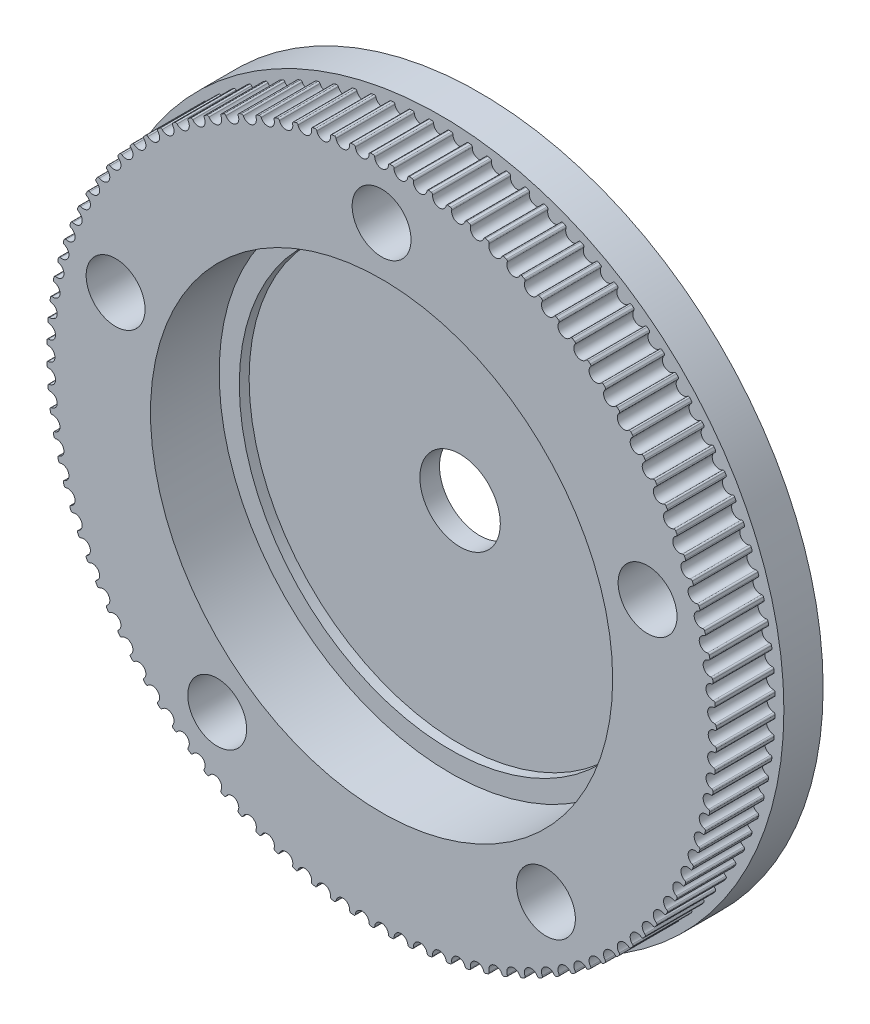
SolidWorks part; units mm, degrees
ref_plane "前视基准面" through (0, 0, 0) normal (0, 0, 1) x (1, 0, 0)
ref_plane "上视基准面" through (0, 0, 0) normal (0, 1, 0) x (1, 0, 0)
ref_plane "右视基准面" through (0, 0, 0) normal (1, 0, 0) x (0, 0, -1)
sketch "草图1" plane through (0, 0, 0) normal (0, 0, 1) x (1, 0, 0)
  circle A0 centre (0, 0) radius 35
  circle A1 centre (0, 0) radius 4.1
  dimension "D1" = 70
  dimension "D2" = 8.2
extrude "凸台-拉伸1" add sketch "草图1" along normal blind 4
sketch "草图2" plane through (0, 0, 4) normal (0, 0, 1) x (1, 0, 0)
  circle A0 centre (0, 0) radius 4.1 construction
  circle A1 centre (0, 0) radius 4.1
  arc B0 (1.1216, 34.1041) -> (0.8633, 34.1116) centre (0, 0) ccw
  arc B1 (1.2763, 33.9415) -> (1.1216, 34.1041) centre (1.1163, 33.9441) ccw
  arc B2 (0.8633, 34.1116) -> (0.6994, 33.9583) centre (0.8593, 33.9516) ccw
  arc B3 (1.2763, 33.9415) -> (2.6727, 33.8602) centre (1.9762, 33.93) ccw
  arc B4 (-0.8633, 34.1116) -> (-1.1216, 34.1041) centre (0, 0) ccw
  arc B5 (-0.6994, 33.9583) -> (-0.8633, 34.1116) centre (-0.8593, 33.9516) ccw
  arc B6 (-1.1216, 34.1041) -> (-1.2763, 33.9415) centre (-1.1163, 33.9441) ccw
  arc B7 (-0.6994, 33.9583) -> (0.6994, 33.9583) centre (0, 33.9875) ccw
  arc B8 (-2.8453, 34.0037) -> (-3.1027, 33.9812) centre (0, 0) ccw
  arc B9 (-2.6727, 33.8602) -> (-2.8453, 34.0037) centre (-2.8319, 33.8442) ccw
  arc B10 (-3.1027, 33.9812) -> (-3.2477, 33.8099) centre (-3.0881, 33.8218) ccw
  arc B11 (-2.6727, 33.8602) -> (-1.2763, 33.9415) centre (-1.9762, 33.93) ccw
  arc B12 (-4.8176, 33.7807) -> (-5.0732, 33.7433) centre (0, 0) ccw
  arc B13 (-4.637, 33.6475) -> (-4.8176, 33.7807) centre (-4.795, 33.6223) ccw
  arc B14 (-5.0732, 33.7433) -> (-5.208, 33.5638) centre (-5.0494, 33.585) ccw
  arc B15 (-4.637, 33.6475) -> (-3.2477, 33.8099) centre (-3.9457, 33.7577) ccw
  arc B16 (-6.7736, 33.4434) -> (-7.0266, 33.3912) centre (0, 0) ccw
  arc B17 (-6.5856, 33.321) -> (-6.7736, 33.4434) centre (-6.7418, 33.2866) ccw
  arc B18 (-7.0266, 33.3912) -> (-7.1508, 33.2042) centre (-6.9937, 33.2346) ccw
  arc B19 (-6.5856, 33.321) -> (-5.208, 33.5638) centre (-5.9019, 33.4712) ccw
  arc B20 (-8.7067, 32.993) -> (-8.9563, 32.9261) centre (0, 0) ccw
  arc B21 (-8.5119, 32.8817) -> (-8.7067, 32.993) centre (-8.6659, 32.8383) ccw
  arc B22 (-8.9563, 32.9261) -> (-9.0693, 32.7323) centre (-8.9143, 32.7717) ccw
  arc B23 (-8.5119, 32.8817) -> (-7.1508, 33.2042) centre (-7.8381, 33.0714) ccw
  arc B24 (-10.6103, 32.4309) -> (-10.8556, 32.3497) centre (0, 0) ccw
  arc B25 (-10.4094, 32.3311) -> (-10.6103, 32.4309) centre (-10.5606, 32.2789) ccw
  arc B26 (-10.8556, 32.3497) -> (-10.9572, 32.1496) centre (-10.8047, 32.198) ccw
  arc B27 (-10.4094, 32.3311) -> (-9.0693, 32.7323) centre (-9.7477, 32.5597) ccw
  arc B28 (-12.4781, 31.7591) -> (-12.7182, 31.6637) centre (0, 0) ccw
  arc B29 (-12.2716, 31.6712) -> (-12.4781, 31.7591) centre (-12.4196, 31.6102) ccw
  arc B30 (-12.7182, 31.6637) -> (-12.808, 31.4581) centre (-12.6586, 31.5153) ccw
  arc B31 (-12.2716, 31.6712) -> (-10.9572, 32.1496) centre (-11.6244, 31.9378) ccw
  arc B32 (-14.3036, 30.9799) -> (-14.5378, 30.8707) centre (0, 0) ccw
  arc B33 (-14.0924, 30.904) -> (-14.3036, 30.9799) centre (-14.2365, 30.8346) ccw
  arc B34 (-14.5378, 30.8707) -> (-14.6155, 30.6601) centre (-14.4696, 30.7259) ccw
  arc B35 (-14.0924, 30.904) -> (-12.808, 31.4581) centre (-13.4618, 31.2079) ccw
  arc B36 (-16.0807, 30.0958) -> (-16.3081, 29.9731) centre (0, 0) ccw
  arc B37 (-15.8655, 30.0324) -> (-16.0807, 30.0958) centre (-16.0053, 29.9547) ccw
  arc B38 (-16.3081, 29.9731) -> (-16.3735, 29.7584) centre (-16.2317, 29.8326) ccw
  arc B39 (-15.8655, 30.0324) -> (-14.6155, 30.6601) centre (-15.2536, 30.3723) ccw
  arc B40 (-17.8034, 29.1098) -> (-18.0233, 28.9742) centre (0, 0) ccw
  arc B41 (-17.5848, 29.0591) -> (-17.8034, 29.1098) centre (-17.7199, 28.9733) ccw
  arc B42 (-18.0233, 28.9742) -> (-18.0761, 28.7561) centre (-17.9388, 28.8383) ccw
  arc B43 (-17.5848, 29.0591) -> (-16.3735, 29.7584) centre (-16.9937, 29.434) ccw
  arc B44 (-19.4659, 28.0254) -> (-19.6775, 27.8772) centre (0, 0) ccw
  arc B45 (-19.2447, 27.9874) -> (-19.4659, 28.0254) centre (-19.3746, 27.894) ccw
  arc B46 (-19.6775, 27.8772) -> (-19.7175, 27.6564) centre (-19.5853, 27.7465) ccw
  arc B47 (-19.2447, 27.9874) -> (-18.0761, 28.7561) centre (-18.6764, 28.3961) ccw
  arc B48 (-21.0625, 26.8462) -> (-21.2652, 26.6859) centre (0, 0) ccw
  arc B49 (-20.8395, 26.8211) -> (-21.0625, 26.8462) centre (-20.9637, 26.7203) ccw
  arc B50 (-21.2652, 26.6859) -> (-21.2922, 26.4631) centre (-21.1655, 26.5608) ccw
  arc B51 (-20.8395, 26.8211) -> (-19.7175, 27.6564) centre (-20.2959, 27.2622) ccw
  arc B52 (-22.5878, 25.5761) -> (-22.7808, 25.4043) centre (0, 0) ccw
  arc B53 (-22.3637, 25.564) -> (-22.5878, 25.5761) centre (-22.4819, 25.4561) ccw
  arc B54 (-22.7808, 25.4043) -> (-22.7949, 25.1803) centre (-22.674, 25.2852) ccw
  arc B55 (-22.3637, 25.564) -> (-21.2922, 26.4631) centre (-21.8467, 26.0359) ccw
  arc B56 (-24.0367, 24.2194) -> (-24.2194, 24.0367) centre (0, 0) ccw
  arc B57 (-23.8123, 24.2204) -> (-24.0367, 24.2194) centre (-23.924, 24.1059) ccw
  arc B58 (-24.2194, 24.0367) -> (-24.2204, 23.8123) centre (-24.1059, 23.924) ccw
  arc B59 (-23.8123, 24.2204) -> (-22.7949, 25.1803) centre (-23.3236, 24.7216) ccw
  arc B60 (-25.4043, 22.7808) -> (-25.5761, 22.5878) centre (0, 0) ccw
  arc B61 (-25.1803, 22.7949) -> (-25.4043, 22.7808) centre (-25.2852, 22.674) ccw
  arc B62 (-25.5761, 22.5878) -> (-25.564, 22.3637) centre (-25.4561, 22.4819) ccw
  arc B63 (-25.1803, 22.7949) -> (-24.2204, 23.8123) centre (-24.7216, 23.3236) ccw
  arc B64 (-26.6859, 21.2652) -> (-26.8462, 21.0625) centre (0, 0) ccw
  arc B65 (-26.4631, 21.2922) -> (-26.6859, 21.2652) centre (-26.5608, 21.1655) ccw
  arc B66 (-26.8462, 21.0625) -> (-26.8211, 20.8395) centre (-26.7203, 20.9637) ccw
  arc B67 (-26.4631, 21.2922) -> (-25.564, 22.3637) centre (-26.0359, 21.8467) ccw
  arc B68 (-27.8772, 19.6775) -> (-28.0254, 19.4659) centre (0, 0) ccw
  arc B69 (-27.6564, 19.7175) -> (-27.8772, 19.6775) centre (-27.7465, 19.5853) ccw
  arc B70 (-28.0254, 19.4659) -> (-27.9874, 19.2447) centre (-27.894, 19.3746) ccw
  arc B71 (-27.6564, 19.7175) -> (-26.8211, 20.8395) centre (-27.2622, 20.2959) ccw
  arc B72 (-28.9742, 18.0233) -> (-29.1098, 17.8034) centre (0, 0) ccw
  arc B73 (-28.7561, 18.0761) -> (-28.9742, 18.0233) centre (-28.8383, 17.9388) ccw
  arc B74 (-29.1098, 17.8034) -> (-29.0591, 17.5848) centre (-28.9733, 17.7199) ccw
  arc B75 (-28.7561, 18.0761) -> (-27.9874, 19.2447) centre (-28.3961, 18.6764) ccw
  arc B76 (-29.9731, 16.3081) -> (-30.0958, 16.0807) centre (0, 0) ccw
  arc B77 (-29.7584, 16.3735) -> (-29.9731, 16.3081) centre (-29.8326, 16.2317) ccw
  arc B78 (-30.0958, 16.0807) -> (-30.0324, 15.8655) centre (-29.9547, 16.0053) ccw
  arc B79 (-29.7584, 16.3735) -> (-29.0591, 17.5848) centre (-29.434, 16.9937) ccw
  arc B80 (-30.8707, 14.5378) -> (-30.9799, 14.3036) centre (0, 0) ccw
  arc B81 (-30.6601, 14.6155) -> (-30.8707, 14.5378) centre (-30.7259, 14.4696) ccw
  arc B82 (-30.9799, 14.3036) -> (-30.904, 14.0924) centre (-30.8346, 14.2365) ccw
  arc B83 (-30.6601, 14.6155) -> (-30.0324, 15.8655) centre (-30.3723, 15.2536) ccw
  arc B84 (-31.6637, 12.7182) -> (-31.7591, 12.4781) centre (0, 0) ccw
  arc B85 (-31.4581, 12.808) -> (-31.6637, 12.7182) centre (-31.5153, 12.6586) ccw
  arc B86 (-31.7591, 12.4781) -> (-31.6712, 12.2716) centre (-31.6102, 12.4196) ccw
  arc B87 (-31.4581, 12.808) -> (-30.904, 14.0924) centre (-31.2079, 13.4618) ccw
  arc B88 (-32.3497, 10.8556) -> (-32.4309, 10.6103) centre (0, 0) ccw
  arc B89 (-32.1496, 10.9572) -> (-32.3497, 10.8556) centre (-32.198, 10.8047) ccw
  arc B90 (-32.4309, 10.6103) -> (-32.3311, 10.4094) centre (-32.2789, 10.5606) ccw
  arc B91 (-32.1496, 10.9572) -> (-31.6712, 12.2716) centre (-31.9378, 11.6244) ccw
  arc B92 (-32.9261, 8.9563) -> (-32.993, 8.7067) centre (0, 0) ccw
  arc B93 (-32.7323, 9.0693) -> (-32.9261, 8.9563) centre (-32.7717, 8.9143) ccw
  arc B94 (-32.993, 8.7067) -> (-32.8817, 8.5119) centre (-32.8383, 8.6659) ccw
  arc B95 (-32.7323, 9.0693) -> (-32.3311, 10.4094) centre (-32.5597, 9.7477) ccw
  arc B96 (-33.3912, 7.0266) -> (-33.4434, 6.7736) centre (0, 0) ccw
  arc B97 (-33.2042, 7.1508) -> (-33.3912, 7.0266) centre (-33.2346, 6.9937) ccw
  arc B98 (-33.4434, 6.7736) -> (-33.321, 6.5856) centre (-33.2866, 6.7418) ccw
  arc B99 (-33.2042, 7.1508) -> (-32.8817, 8.5119) centre (-33.0714, 7.8381) ccw
  arc B100 (-33.7433, 5.0732) -> (-33.7807, 4.8176) centre (0, 0) ccw
  arc B101 (-33.5638, 5.208) -> (-33.7433, 5.0732) centre (-33.585, 5.0494) ccw
  arc B102 (-33.7807, 4.8176) -> (-33.6475, 4.637) centre (-33.6223, 4.795) ccw
  arc B103 (-33.5638, 5.208) -> (-33.321, 6.5856) centre (-33.4712, 5.9019) ccw
  arc B104 (-33.9812, 3.1027) -> (-34.0037, 2.8453) centre (0, 0) ccw
  arc B105 (-33.8099, 3.2477) -> (-33.9812, 3.1027) centre (-33.8218, 3.0881) ccw
  arc B106 (-34.0037, 2.8453) -> (-33.8602, 2.6727) centre (-33.8442, 2.8319) ccw
  arc B107 (-33.8099, 3.2477) -> (-33.6475, 4.637) centre (-33.7577, 3.9457) ccw
  arc B108 (-34.1041, 1.1216) -> (-34.1116, 0.8633) centre (0, 0) ccw
  arc B109 (-33.9415, 1.2763) -> (-34.1041, 1.1216) centre (-33.9441, 1.1163) ccw
  arc B110 (-34.1116, 0.8633) -> (-33.9583, 0.6994) centre (-33.9516, 0.8593) ccw
  arc B111 (-33.9415, 1.2763) -> (-33.8602, 2.6727) centre (-33.93, 1.9762) ccw
  arc B112 (-34.1116, -0.8633) -> (-34.1041, -1.1216) centre (0, 0) ccw
  arc B113 (-33.9583, -0.6994) -> (-34.1116, -0.8633) centre (-33.9516, -0.8593) ccw
  arc B114 (-34.1041, -1.1216) -> (-33.9415, -1.2763) centre (-33.9441, -1.1163) ccw
  arc B115 (-33.9583, -0.6994) -> (-33.9583, 0.6994) centre (-33.9875, 0) ccw
  arc B116 (-34.0037, -2.8453) -> (-33.9812, -3.1027) centre (0, 0) ccw
  arc B117 (-33.8602, -2.6727) -> (-34.0037, -2.8453) centre (-33.8442, -2.8319) ccw
  arc B118 (-33.9812, -3.1027) -> (-33.8099, -3.2477) centre (-33.8218, -3.0881) ccw
  arc B119 (-33.8602, -2.6727) -> (-33.9415, -1.2763) centre (-33.93, -1.9762) ccw
  arc B120 (-33.7807, -4.8176) -> (-33.7433, -5.0732) centre (0, 0) ccw
  arc B121 (-33.6475, -4.637) -> (-33.7807, -4.8176) centre (-33.6223, -4.795) ccw
  arc B122 (-33.7433, -5.0732) -> (-33.5638, -5.208) centre (-33.585, -5.0494) ccw
  arc B123 (-33.6475, -4.637) -> (-33.8099, -3.2477) centre (-33.7577, -3.9457) ccw
  arc B124 (-33.4434, -6.7736) -> (-33.3912, -7.0266) centre (0, 0) ccw
  arc B125 (-33.321, -6.5856) -> (-33.4434, -6.7736) centre (-33.2866, -6.7418) ccw
  arc B126 (-33.3912, -7.0266) -> (-33.2042, -7.1508) centre (-33.2346, -6.9937) ccw
  arc B127 (-33.321, -6.5856) -> (-33.5638, -5.208) centre (-33.4712, -5.9019) ccw
  arc B128 (-32.993, -8.7067) -> (-32.9261, -8.9563) centre (0, 0) ccw
  arc B129 (-32.8817, -8.5119) -> (-32.993, -8.7067) centre (-32.8383, -8.6659) ccw
  arc B130 (-32.9261, -8.9563) -> (-32.7323, -9.0693) centre (-32.7717, -8.9143) ccw
  arc B131 (-32.8817, -8.5119) -> (-33.2042, -7.1508) centre (-33.0714, -7.8381) ccw
  arc B132 (-32.4309, -10.6103) -> (-32.3497, -10.8556) centre (0, 0) ccw
  arc B133 (-32.3311, -10.4094) -> (-32.4309, -10.6103) centre (-32.2789, -10.5606) ccw
  arc B134 (-32.3497, -10.8556) -> (-32.1496, -10.9572) centre (-32.198, -10.8047) ccw
  arc B135 (-32.3311, -10.4094) -> (-32.7323, -9.0693) centre (-32.5597, -9.7477) ccw
  arc B136 (-31.7591, -12.4781) -> (-31.6637, -12.7182) centre (0, 0) ccw
  arc B137 (-31.6712, -12.2716) -> (-31.7591, -12.4781) centre (-31.6102, -12.4196) ccw
  arc B138 (-31.6637, -12.7182) -> (-31.4581, -12.808) centre (-31.5153, -12.6586) ccw
  arc B139 (-31.6712, -12.2716) -> (-32.1496, -10.9572) centre (-31.9378, -11.6244) ccw
  arc B140 (-30.9799, -14.3036) -> (-30.8707, -14.5378) centre (0, 0) ccw
  arc B141 (-30.904, -14.0924) -> (-30.9799, -14.3036) centre (-30.8346, -14.2365) ccw
  arc B142 (-30.8707, -14.5378) -> (-30.6601, -14.6155) centre (-30.7259, -14.4696) ccw
  arc B143 (-30.904, -14.0924) -> (-31.4581, -12.808) centre (-31.2079, -13.4618) ccw
  arc B144 (-30.0958, -16.0807) -> (-29.9731, -16.3081) centre (0, 0) ccw
  arc B145 (-30.0324, -15.8655) -> (-30.0958, -16.0807) centre (-29.9547, -16.0053) ccw
  arc B146 (-29.9731, -16.3081) -> (-29.7584, -16.3735) centre (-29.8326, -16.2317) ccw
  arc B147 (-30.0324, -15.8655) -> (-30.6601, -14.6155) centre (-30.3723, -15.2536) ccw
  arc B148 (-29.1098, -17.8034) -> (-28.9742, -18.0233) centre (0, 0) ccw
  arc B149 (-29.0591, -17.5848) -> (-29.1098, -17.8034) centre (-28.9733, -17.7199) ccw
  arc B150 (-28.9742, -18.0233) -> (-28.7561, -18.0761) centre (-28.8383, -17.9388) ccw
  arc B151 (-29.0591, -17.5848) -> (-29.7584, -16.3735) centre (-29.434, -16.9938) ccw
  arc B152 (-28.0254, -19.4659) -> (-27.8772, -19.6775) centre (0, 0) ccw
  arc B153 (-27.9874, -19.2447) -> (-28.0254, -19.4659) centre (-27.894, -19.3746) ccw
  arc B154 (-27.8772, -19.6775) -> (-27.6564, -19.7175) centre (-27.7465, -19.5853) ccw
  arc B155 (-27.9874, -19.2447) -> (-28.7561, -18.0761) centre (-28.3961, -18.6764) ccw
  arc B156 (-26.8462, -21.0625) -> (-26.6859, -21.2652) centre (0, 0) ccw
  arc B157 (-26.8211, -20.8395) -> (-26.8462, -21.0625) centre (-26.7203, -20.9637) ccw
  arc B158 (-26.6859, -21.2652) -> (-26.4631, -21.2922) centre (-26.5608, -21.1655) ccw
  arc B159 (-26.8211, -20.8395) -> (-27.6564, -19.7175) centre (-27.2622, -20.2959) ccw
  arc B160 (-25.5761, -22.5878) -> (-25.4043, -22.7808) centre (0, 0) ccw
  arc B161 (-25.564, -22.3637) -> (-25.5761, -22.5878) centre (-25.4561, -22.4819) ccw
  arc B162 (-25.4043, -22.7808) -> (-25.1803, -22.7949) centre (-25.2852, -22.674) ccw
  arc B163 (-25.564, -22.3637) -> (-26.4631, -21.2922) centre (-26.0359, -21.8467) ccw
  arc B164 (-24.2194, -24.0367) -> (-24.0367, -24.2194) centre (0, 0) ccw
  arc B165 (-24.2204, -23.8123) -> (-24.2194, -24.0367) centre (-24.1059, -23.924) ccw
  arc B166 (-24.0367, -24.2194) -> (-23.8123, -24.2204) centre (-23.924, -24.1059) ccw
  arc B167 (-24.2204, -23.8123) -> (-25.1803, -22.7949) centre (-24.7216, -23.3236) ccw
  arc B168 (-22.7808, -25.4043) -> (-22.5878, -25.5761) centre (0, 0) ccw
  arc B169 (-22.7949, -25.1803) -> (-22.7808, -25.4043) centre (-22.674, -25.2852) ccw
  arc B170 (-22.5878, -25.5761) -> (-22.3637, -25.564) centre (-22.4819, -25.4561) ccw
  arc B171 (-22.7949, -25.1803) -> (-23.8123, -24.2204) centre (-23.3236, -24.7216) ccw
  arc B172 (-21.2652, -26.6859) -> (-21.0625, -26.8462) centre (0, 0) ccw
  arc B173 (-21.2922, -26.4631) -> (-21.2652, -26.6859) centre (-21.1655, -26.5608) ccw
  arc B174 (-21.0625, -26.8462) -> (-20.8395, -26.8211) centre (-20.9637, -26.7203) ccw
  arc B175 (-21.2922, -26.4631) -> (-22.3637, -25.564) centre (-21.8467, -26.0359) ccw
  arc B176 (-19.6775, -27.8772) -> (-19.4659, -28.0254) centre (0, 0) ccw
  arc B177 (-19.7175, -27.6564) -> (-19.6775, -27.8772) centre (-19.5853, -27.7465) ccw
  arc B178 (-19.4659, -28.0254) -> (-19.2447, -27.9874) centre (-19.3746, -27.894) ccw
  arc B179 (-19.7175, -27.6564) -> (-20.8395, -26.8211) centre (-20.2959, -27.2622) ccw
  arc B180 (-18.0233, -28.9742) -> (-17.8034, -29.1098) centre (0, 0) ccw
  arc B181 (-18.0761, -28.7561) -> (-18.0233, -28.9742) centre (-17.9388, -28.8383) ccw
  arc B182 (-17.8034, -29.1098) -> (-17.5848, -29.0591) centre (-17.7199, -28.9733) ccw
  arc B183 (-18.0761, -28.7561) -> (-19.2447, -27.9874) centre (-18.6764, -28.3961) ccw
  arc B184 (-16.3081, -29.9731) -> (-16.0807, -30.0958) centre (0, 0) ccw
  arc B185 (-16.3735, -29.7584) -> (-16.3081, -29.9731) centre (-16.2317, -29.8326) ccw
  arc B186 (-16.0807, -30.0958) -> (-15.8655, -30.0324) centre (-16.0053, -29.9547) ccw
  arc B187 (-16.3735, -29.7584) -> (-17.5848, -29.0591) centre (-16.9937, -29.434) ccw
  arc B188 (-14.5378, -30.8707) -> (-14.3036, -30.9799) centre (0, 0) ccw
  arc B189 (-14.6155, -30.6601) -> (-14.5378, -30.8707) centre (-14.4696, -30.7259) ccw
  arc B190 (-14.3036, -30.9799) -> (-14.0924, -30.904) centre (-14.2365, -30.8346) ccw
  arc B191 (-14.6155, -30.6601) -> (-15.8655, -30.0324) centre (-15.2536, -30.3723) ccw
  arc B192 (-12.7182, -31.6637) -> (-12.4781, -31.7591) centre (0, 0) ccw
  arc B193 (-12.808, -31.4581) -> (-12.7182, -31.6637) centre (-12.6586, -31.5153) ccw
  arc B194 (-12.4781, -31.7591) -> (-12.2716, -31.6712) centre (-12.4196, -31.6102) ccw
  arc B195 (-12.808, -31.4581) -> (-14.0924, -30.904) centre (-13.4618, -31.2079) ccw
  arc B196 (-10.8556, -32.3497) -> (-10.6103, -32.4309) centre (0, 0) ccw
  arc B197 (-10.9572, -32.1496) -> (-10.8556, -32.3497) centre (-10.8047, -32.198) ccw
  arc B198 (-10.6103, -32.4309) -> (-10.4094, -32.3311) centre (-10.5606, -32.2789) ccw
  arc B199 (-10.9572, -32.1496) -> (-12.2716, -31.6712) centre (-11.6244, -31.9378) ccw
  arc B200 (-8.9563, -32.9261) -> (-8.7067, -32.993) centre (0, 0) ccw
  arc B201 (-9.0693, -32.7323) -> (-8.9563, -32.9261) centre (-8.9143, -32.7717) ccw
  arc B202 (-8.7067, -32.993) -> (-8.5119, -32.8817) centre (-8.6659, -32.8383) ccw
  arc B203 (-9.0693, -32.7323) -> (-10.4094, -32.3311) centre (-9.7477, -32.5597) ccw
  arc B204 (-7.0266, -33.3912) -> (-6.7736, -33.4434) centre (0, 0) ccw
  arc B205 (-7.1508, -33.2042) -> (-7.0266, -33.3912) centre (-6.9937, -33.2346) ccw
  arc B206 (-6.7736, -33.4434) -> (-6.5856, -33.321) centre (-6.7418, -33.2866) ccw
  arc B207 (-7.1508, -33.2042) -> (-8.5119, -32.8817) centre (-7.8381, -33.0714) ccw
  arc B208 (-5.0732, -33.7433) -> (-4.8176, -33.7807) centre (0, 0) ccw
  arc B209 (-5.208, -33.5638) -> (-5.0732, -33.7433) centre (-5.0494, -33.585) ccw
  arc B210 (-4.8176, -33.7807) -> (-4.637, -33.6475) centre (-4.795, -33.6223) ccw
  arc B211 (-5.208, -33.5638) -> (-6.5856, -33.321) centre (-5.9019, -33.4712) ccw
  arc B212 (-3.1027, -33.9812) -> (-2.8453, -34.0037) centre (0, 0) ccw
  arc B213 (-3.2477, -33.8099) -> (-3.1027, -33.9812) centre (-3.0881, -33.8218) ccw
  arc B214 (-2.8453, -34.0037) -> (-2.6727, -33.8602) centre (-2.8319, -33.8442) ccw
  arc B215 (-3.2477, -33.8099) -> (-4.637, -33.6475) centre (-3.9457, -33.7577) ccw
  arc B216 (-1.1216, -34.1041) -> (-0.8633, -34.1116) centre (0, 0) ccw
  arc B217 (-1.2763, -33.9415) -> (-1.1216, -34.1041) centre (-1.1163, -33.9441) ccw
  arc B218 (-0.8633, -34.1116) -> (-0.6994, -33.9583) centre (-0.8593, -33.9516) ccw
  arc B219 (-1.2763, -33.9415) -> (-2.6727, -33.8602) centre (-1.9762, -33.93) ccw
  arc B220 (0.8633, -34.1116) -> (1.1216, -34.1041) centre (0, 0) ccw
  arc B221 (0.6994, -33.9583) -> (0.8633, -34.1116) centre (0.8593, -33.9516) ccw
  arc B222 (1.1216, -34.1041) -> (1.2763, -33.9415) centre (1.1163, -33.9441) ccw
  arc B223 (0.6994, -33.9583) -> (-0.6994, -33.9583) centre (0, -33.9875) ccw
  arc B224 (2.8453, -34.0037) -> (3.1027, -33.9812) centre (0, 0) ccw
  arc B225 (2.6727, -33.8602) -> (2.8453, -34.0037) centre (2.8319, -33.8442) ccw
  arc B226 (3.1027, -33.9812) -> (3.2477, -33.8099) centre (3.0881, -33.8218) ccw
  arc B227 (2.6727, -33.8602) -> (1.2763, -33.9415) centre (1.9762, -33.93) ccw
  arc B228 (4.8176, -33.7807) -> (5.0732, -33.7433) centre (0, 0) ccw
  arc B229 (4.637, -33.6475) -> (4.8176, -33.7807) centre (4.795, -33.6223) ccw
  arc B230 (5.0732, -33.7433) -> (5.208, -33.5638) centre (5.0494, -33.585) ccw
  arc B231 (4.637, -33.6475) -> (3.2477, -33.8099) centre (3.9457, -33.7577) ccw
  arc B232 (6.7736, -33.4434) -> (7.0266, -33.3912) centre (0, 0) ccw
  arc B233 (6.5856, -33.321) -> (6.7736, -33.4434) centre (6.7418, -33.2866) ccw
  arc B234 (7.0266, -33.3912) -> (7.1508, -33.2042) centre (6.9937, -33.2346) ccw
  arc B235 (6.5856, -33.321) -> (5.208, -33.5638) centre (5.9019, -33.4712) ccw
  arc B236 (8.7067, -32.993) -> (8.9563, -32.9261) centre (0, 0) ccw
  arc B237 (8.5119, -32.8817) -> (8.7067, -32.993) centre (8.6659, -32.8383) ccw
  arc B238 (8.9563, -32.9261) -> (9.0693, -32.7323) centre (8.9143, -32.7717) ccw
  arc B239 (8.5119, -32.8817) -> (7.1508, -33.2042) centre (7.8381, -33.0714) ccw
  arc B240 (10.6103, -32.4309) -> (10.8556, -32.3497) centre (0, 0) ccw
  arc B241 (10.4094, -32.3311) -> (10.6103, -32.4309) centre (10.5606, -32.2789) ccw
  arc B242 (10.8556, -32.3497) -> (10.9572, -32.1496) centre (10.8047, -32.198) ccw
  arc B243 (10.4094, -32.3311) -> (9.0693, -32.7323) centre (9.7477, -32.5597) ccw
  arc B244 (12.4781, -31.7591) -> (12.7182, -31.6637) centre (0, 0) ccw
  arc B245 (12.2716, -31.6712) -> (12.4781, -31.7591) centre (12.4196, -31.6102) ccw
  arc B246 (12.7182, -31.6637) -> (12.808, -31.4581) centre (12.6586, -31.5153) ccw
  arc B247 (12.2716, -31.6712) -> (10.9572, -32.1496) centre (11.6244, -31.9378) ccw
  arc B248 (14.3036, -30.9799) -> (14.5378, -30.8707) centre (0, 0) ccw
  arc B249 (14.0924, -30.904) -> (14.3036, -30.9799) centre (14.2365, -30.8346) ccw
  arc B250 (14.5378, -30.8707) -> (14.6155, -30.6601) centre (14.4696, -30.7259) ccw
  arc B251 (14.0924, -30.904) -> (12.808, -31.4581) centre (13.4618, -31.2079) ccw
  arc B252 (16.0807, -30.0958) -> (16.3081, -29.9731) centre (0, 0) ccw
  arc B253 (15.8655, -30.0324) -> (16.0807, -30.0958) centre (16.0053, -29.9547) ccw
  arc B254 (16.3081, -29.9731) -> (16.3735, -29.7584) centre (16.2317, -29.8326) ccw
  arc B255 (15.8655, -30.0324) -> (14.6155, -30.6601) centre (15.2536, -30.3723) ccw
  arc B256 (17.8034, -29.1098) -> (18.0233, -28.9742) centre (0, 0) ccw
  arc B257 (17.5848, -29.0591) -> (17.8034, -29.1098) centre (17.7199, -28.9733) ccw
  arc B258 (18.0233, -28.9742) -> (18.0761, -28.7561) centre (17.9388, -28.8383) ccw
  arc B259 (17.5848, -29.0591) -> (16.3735, -29.7584) centre (16.9938, -29.434) ccw
  arc B260 (19.4659, -28.0254) -> (19.6775, -27.8772) centre (0, 0) ccw
  arc B261 (19.2447, -27.9874) -> (19.4659, -28.0254) centre (19.3746, -27.894) ccw
  arc B262 (19.6775, -27.8772) -> (19.7175, -27.6564) centre (19.5853, -27.7465) ccw
  arc B263 (19.2447, -27.9874) -> (18.0761, -28.7561) centre (18.6764, -28.3961) ccw
  arc B264 (21.0625, -26.8462) -> (21.2652, -26.6859) centre (0, 0) ccw
  arc B265 (20.8395, -26.8211) -> (21.0625, -26.8462) centre (20.9637, -26.7203) ccw
  arc B266 (21.2652, -26.6859) -> (21.2922, -26.4631) centre (21.1655, -26.5608) ccw
  arc B267 (20.8395, -26.8211) -> (19.7175, -27.6564) centre (20.2959, -27.2622) ccw
  arc B268 (22.5878, -25.5761) -> (22.7808, -25.4043) centre (0, 0) ccw
  arc B269 (22.3637, -25.564) -> (22.5878, -25.5761) centre (22.4819, -25.4561) ccw
  arc B270 (22.7808, -25.4043) -> (22.7949, -25.1803) centre (22.674, -25.2852) ccw
  arc B271 (22.3637, -25.564) -> (21.2922, -26.4631) centre (21.8467, -26.0359) ccw
  arc B272 (24.0367, -24.2194) -> (24.2194, -24.0367) centre (0, 0) ccw
  arc B273 (23.8123, -24.2204) -> (24.0367, -24.2194) centre (23.924, -24.1059) ccw
  arc B274 (24.2194, -24.0367) -> (24.2204, -23.8123) centre (24.1059, -23.924) ccw
  arc B275 (23.8123, -24.2204) -> (22.7949, -25.1803) centre (23.3236, -24.7216) ccw
  arc B276 (25.4043, -22.7808) -> (25.5761, -22.5878) centre (0, 0) ccw
  arc B277 (25.1803, -22.7949) -> (25.4043, -22.7808) centre (25.2852, -22.674) ccw
  arc B278 (25.5761, -22.5878) -> (25.564, -22.3637) centre (25.4561, -22.4819) ccw
  arc B279 (25.1803, -22.7949) -> (24.2204, -23.8123) centre (24.7216, -23.3236) ccw
  arc B280 (26.6859, -21.2652) -> (26.8462, -21.0625) centre (0, 0) ccw
  arc B281 (26.4631, -21.2922) -> (26.6859, -21.2652) centre (26.5608, -21.1655) ccw
  arc B282 (26.8462, -21.0625) -> (26.8211, -20.8395) centre (26.7203, -20.9637) ccw
  arc B283 (26.4631, -21.2922) -> (25.564, -22.3637) centre (26.0359, -21.8467) ccw
  arc B284 (27.8772, -19.6775) -> (28.0254, -19.4659) centre (0, 0) ccw
  arc B285 (27.6564, -19.7175) -> (27.8772, -19.6775) centre (27.7465, -19.5853) ccw
  arc B286 (28.0254, -19.4659) -> (27.9874, -19.2447) centre (27.894, -19.3746) ccw
  arc B287 (27.6564, -19.7175) -> (26.8211, -20.8395) centre (27.2622, -20.2959) ccw
  arc B288 (28.9742, -18.0233) -> (29.1098, -17.8034) centre (0, 0) ccw
  arc B289 (28.7561, -18.0761) -> (28.9742, -18.0233) centre (28.8383, -17.9388) ccw
  arc B290 (29.1098, -17.8034) -> (29.0591, -17.5848) centre (28.9733, -17.7199) ccw
  arc B291 (28.7561, -18.0761) -> (27.9874, -19.2447) centre (28.3961, -18.6764) ccw
  arc B292 (29.9731, -16.3081) -> (30.0958, -16.0807) centre (0, 0) ccw
  arc B293 (29.7584, -16.3735) -> (29.9731, -16.3081) centre (29.8326, -16.2317) ccw
  arc B294 (30.0958, -16.0807) -> (30.0324, -15.8655) centre (29.9547, -16.0053) ccw
  arc B295 (29.7584, -16.3735) -> (29.0591, -17.5848) centre (29.434, -16.9938) ccw
  arc B296 (30.8707, -14.5378) -> (30.9799, -14.3036) centre (0, 0) ccw
  arc B297 (30.6601, -14.6155) -> (30.8707, -14.5378) centre (30.7259, -14.4696) ccw
  arc B298 (30.9799, -14.3036) -> (30.904, -14.0924) centre (30.8346, -14.2365) ccw
  arc B299 (30.6601, -14.6155) -> (30.0324, -15.8655) centre (30.3723, -15.2536) ccw
  arc B300 (31.6637, -12.7182) -> (31.7591, -12.4781) centre (0, 0) ccw
  arc B301 (31.4581, -12.808) -> (31.6637, -12.7182) centre (31.5153, -12.6586) ccw
  arc B302 (31.7591, -12.4781) -> (31.6712, -12.2716) centre (31.6102, -12.4196) ccw
  arc B303 (31.4581, -12.808) -> (30.904, -14.0924) centre (31.2079, -13.4618) ccw
  arc B304 (32.3497, -10.8556) -> (32.4309, -10.6103) centre (0, 0) ccw
  arc B305 (32.1496, -10.9572) -> (32.3497, -10.8556) centre (32.198, -10.8047) ccw
  arc B306 (32.4309, -10.6103) -> (32.3311, -10.4094) centre (32.2789, -10.5606) ccw
  arc B307 (32.1496, -10.9572) -> (31.6712, -12.2716) centre (31.9378, -11.6244) ccw
  arc B308 (32.9261, -8.9563) -> (32.993, -8.7067) centre (0, 0) ccw
  arc B309 (32.7323, -9.0693) -> (32.9261, -8.9563) centre (32.7717, -8.9143) ccw
  arc B310 (32.993, -8.7067) -> (32.8817, -8.5119) centre (32.8383, -8.6659) ccw
  arc B311 (32.7323, -9.0693) -> (32.3311, -10.4094) centre (32.5597, -9.7477) ccw
  arc B312 (33.3912, -7.0266) -> (33.4434, -6.7736) centre (0, 0) ccw
  arc B313 (33.2042, -7.1508) -> (33.3912, -7.0266) centre (33.2346, -6.9937) ccw
  arc B314 (33.4434, -6.7736) -> (33.321, -6.5856) centre (33.2866, -6.7418) ccw
  arc B315 (33.2042, -7.1508) -> (32.8817, -8.5119) centre (33.0714, -7.8381) ccw
  arc B316 (33.7433, -5.0732) -> (33.7807, -4.8176) centre (0, 0) ccw
  arc B317 (33.5638, -5.208) -> (33.7433, -5.0732) centre (33.585, -5.0494) ccw
  arc B318 (33.7807, -4.8176) -> (33.6475, -4.637) centre (33.6223, -4.795) ccw
  arc B319 (33.5638, -5.208) -> (33.321, -6.5856) centre (33.4712, -5.9019) ccw
  arc B320 (33.9812, -3.1027) -> (34.0037, -2.8453) centre (0, 0) ccw
  arc B321 (33.8099, -3.2477) -> (33.9812, -3.1027) centre (33.8218, -3.0881) ccw
  arc B322 (34.0037, -2.8453) -> (33.8602, -2.6727) centre (33.8442, -2.8319) ccw
  arc B323 (33.8099, -3.2477) -> (33.6475, -4.637) centre (33.7577, -3.9457) ccw
  arc B324 (34.1041, -1.1216) -> (34.1116, -0.8633) centre (0, 0) ccw
  arc B325 (33.9415, -1.2763) -> (34.1041, -1.1216) centre (33.9441, -1.1163) ccw
  arc B326 (34.1116, -0.8633) -> (33.9583, -0.6994) centre (33.9516, -0.8593) ccw
  arc B327 (33.9415, -1.2763) -> (33.8602, -2.6727) centre (33.93, -1.9762) ccw
  arc B328 (34.1116, 0.8633) -> (34.1041, 1.1216) centre (0, 0) ccw
  arc B329 (33.9583, 0.6994) -> (34.1116, 0.8633) centre (33.9516, 0.8593) ccw
  arc B330 (34.1041, 1.1216) -> (33.9415, 1.2763) centre (33.9441, 1.1163) ccw
  arc B331 (33.9583, 0.6994) -> (33.9583, -0.6994) centre (33.9875, 0) ccw
  arc B332 (34.0037, 2.8453) -> (33.9812, 3.1027) centre (0, 0) ccw
  arc B333 (33.8602, 2.6727) -> (34.0037, 2.8453) centre (33.8442, 2.8319) ccw
  arc B334 (33.9812, 3.1027) -> (33.8099, 3.2477) centre (33.8218, 3.0881) ccw
  arc B335 (33.8602, 2.6727) -> (33.9415, 1.2763) centre (33.93, 1.9762) ccw
  arc B336 (33.7807, 4.8176) -> (33.7433, 5.0732) centre (0, 0) ccw
  arc B337 (33.6475, 4.637) -> (33.7807, 4.8176) centre (33.6223, 4.795) ccw
  arc B338 (33.7433, 5.0732) -> (33.5638, 5.208) centre (33.585, 5.0494) ccw
  arc B339 (33.6475, 4.637) -> (33.8099, 3.2477) centre (33.7577, 3.9457) ccw
  arc B340 (33.4434, 6.7736) -> (33.3912, 7.0266) centre (0, 0) ccw
  arc B341 (33.321, 6.5856) -> (33.4434, 6.7736) centre (33.2866, 6.7418) ccw
  arc B342 (33.3912, 7.0266) -> (33.2042, 7.1508) centre (33.2346, 6.9937) ccw
  arc B343 (33.321, 6.5856) -> (33.5638, 5.208) centre (33.4712, 5.9019) ccw
  arc B344 (32.993, 8.7067) -> (32.9261, 8.9563) centre (0, 0) ccw
  arc B345 (32.8817, 8.5119) -> (32.993, 8.7067) centre (32.8383, 8.6659) ccw
  arc B346 (32.9261, 8.9563) -> (32.7323, 9.0693) centre (32.7717, 8.9143) ccw
  arc B347 (32.8817, 8.5119) -> (33.2042, 7.1508) centre (33.0714, 7.8381) ccw
  arc B348 (32.4309, 10.6103) -> (32.3497, 10.8556) centre (0, 0) ccw
  arc B349 (32.3311, 10.4094) -> (32.4309, 10.6103) centre (32.2789, 10.5606) ccw
  arc B350 (32.3497, 10.8556) -> (32.1496, 10.9572) centre (32.198, 10.8047) ccw
  arc B351 (32.3311, 10.4094) -> (32.7323, 9.0693) centre (32.5597, 9.7477) ccw
  arc B352 (31.7591, 12.4781) -> (31.6637, 12.7182) centre (0, 0) ccw
  arc B353 (31.6712, 12.2716) -> (31.7591, 12.4781) centre (31.6102, 12.4196) ccw
  arc B354 (31.6637, 12.7182) -> (31.4581, 12.808) centre (31.5153, 12.6586) ccw
  arc B355 (31.6712, 12.2716) -> (32.1496, 10.9572) centre (31.9378, 11.6244) ccw
  arc B356 (30.9799, 14.3036) -> (30.8707, 14.5378) centre (0, 0) ccw
  arc B357 (30.904, 14.0924) -> (30.9799, 14.3036) centre (30.8346, 14.2365) ccw
  arc B358 (30.8707, 14.5378) -> (30.6601, 14.6155) centre (30.7259, 14.4696) ccw
  arc B359 (30.904, 14.0924) -> (31.4581, 12.808) centre (31.2079, 13.4618) ccw
  arc B360 (30.0958, 16.0807) -> (29.9731, 16.3081) centre (0, 0) ccw
  arc B361 (30.0324, 15.8655) -> (30.0958, 16.0807) centre (29.9547, 16.0053) ccw
  arc B362 (29.9731, 16.3081) -> (29.7584, 16.3735) centre (29.8326, 16.2317) ccw
  arc B363 (30.0324, 15.8655) -> (30.6601, 14.6155) centre (30.3723, 15.2536) ccw
  arc B364 (29.1098, 17.8034) -> (28.9742, 18.0233) centre (0, 0) ccw
  arc B365 (29.0591, 17.5848) -> (29.1098, 17.8034) centre (28.9733, 17.7199) ccw
  arc B366 (28.9742, 18.0233) -> (28.7561, 18.0761) centre (28.8383, 17.9388) ccw
  arc B367 (29.0591, 17.5848) -> (29.7584, 16.3735) centre (29.434, 16.9938) ccw
  arc B368 (28.0254, 19.4659) -> (27.8772, 19.6775) centre (0, 0) ccw
  arc B369 (27.9874, 19.2447) -> (28.0254, 19.4659) centre (27.894, 19.3746) ccw
  arc B370 (27.8772, 19.6775) -> (27.6564, 19.7175) centre (27.7465, 19.5853) ccw
  arc B371 (27.9874, 19.2447) -> (28.7561, 18.0761) centre (28.3961, 18.6764) ccw
  arc B372 (26.8462, 21.0625) -> (26.6859, 21.2652) centre (0, 0) ccw
  arc B373 (26.8211, 20.8395) -> (26.8462, 21.0625) centre (26.7203, 20.9637) ccw
  arc B374 (26.6859, 21.2652) -> (26.4631, 21.2922) centre (26.5608, 21.1655) ccw
  arc B375 (26.8211, 20.8395) -> (27.6564, 19.7175) centre (27.2622, 20.2959) ccw
  arc B376 (25.5761, 22.5878) -> (25.4043, 22.7808) centre (0, 0) ccw
  arc B377 (25.564, 22.3637) -> (25.5761, 22.5878) centre (25.4561, 22.4819) ccw
  arc B378 (25.4043, 22.7808) -> (25.1803, 22.7949) centre (25.2852, 22.674) ccw
  arc B379 (25.564, 22.3637) -> (26.4631, 21.2922) centre (26.0359, 21.8467) ccw
  arc B380 (24.2194, 24.0367) -> (24.0367, 24.2194) centre (0, 0) ccw
  arc B381 (24.2204, 23.8123) -> (24.2194, 24.0367) centre (24.1059, 23.924) ccw
  arc B382 (24.0367, 24.2194) -> (23.8123, 24.2204) centre (23.924, 24.1059) ccw
  arc B383 (24.2204, 23.8123) -> (25.1803, 22.7949) centre (24.7216, 23.3236) ccw
  arc B384 (22.7808, 25.4043) -> (22.5878, 25.5761) centre (0, 0) ccw
  arc B385 (22.7949, 25.1803) -> (22.7808, 25.4043) centre (22.674, 25.2852) ccw
  arc B386 (22.5878, 25.5761) -> (22.3637, 25.564) centre (22.4819, 25.4561) ccw
  arc B387 (22.7949, 25.1803) -> (23.8123, 24.2204) centre (23.3236, 24.7216) ccw
  arc B388 (21.2652, 26.6859) -> (21.0625, 26.8462) centre (0, 0) ccw
  arc B389 (21.2922, 26.4631) -> (21.2652, 26.6859) centre (21.1655, 26.5608) ccw
  arc B390 (21.0625, 26.8462) -> (20.8395, 26.8211) centre (20.9637, 26.7203) ccw
  arc B391 (21.2922, 26.4631) -> (22.3637, 25.564) centre (21.8467, 26.0359) ccw
  arc B392 (19.6775, 27.8772) -> (19.4659, 28.0254) centre (0, 0) ccw
  arc B393 (19.7175, 27.6564) -> (19.6775, 27.8772) centre (19.5853, 27.7465) ccw
  arc B394 (19.4659, 28.0254) -> (19.2447, 27.9874) centre (19.3746, 27.894) ccw
  arc B395 (19.7175, 27.6564) -> (20.8395, 26.8211) centre (20.2959, 27.2622) ccw
  arc B396 (18.0233, 28.9742) -> (17.8034, 29.1098) centre (0, 0) ccw
  arc B397 (18.0761, 28.7561) -> (18.0233, 28.9742) centre (17.9388, 28.8383) ccw
  arc B398 (17.8034, 29.1098) -> (17.5848, 29.0591) centre (17.7199, 28.9733) ccw
  arc B399 (18.0761, 28.7561) -> (19.2447, 27.9874) centre (18.6764, 28.3961) ccw
  arc B400 (16.3081, 29.9731) -> (16.0807, 30.0958) centre (0, 0) ccw
  arc B401 (16.3735, 29.7584) -> (16.3081, 29.9731) centre (16.2317, 29.8326) ccw
  arc B402 (16.0807, 30.0958) -> (15.8655, 30.0324) centre (16.0053, 29.9547) ccw
  arc B403 (16.3735, 29.7584) -> (17.5848, 29.0591) centre (16.9937, 29.434) ccw
  arc B404 (14.5378, 30.8707) -> (14.3036, 30.9799) centre (0, 0) ccw
  arc B405 (14.6155, 30.6601) -> (14.5378, 30.8707) centre (14.4696, 30.7259) ccw
  arc B406 (14.3036, 30.9799) -> (14.0924, 30.904) centre (14.2365, 30.8346) ccw
  arc B407 (14.6155, 30.6601) -> (15.8655, 30.0324) centre (15.2536, 30.3723) ccw
  arc B408 (12.7182, 31.6637) -> (12.4781, 31.7591) centre (0, 0) ccw
  arc B409 (12.808, 31.4581) -> (12.7182, 31.6637) centre (12.6586, 31.5153) ccw
  arc B410 (12.4781, 31.7591) -> (12.2716, 31.6712) centre (12.4196, 31.6102) ccw
  arc B411 (12.808, 31.4581) -> (14.0924, 30.904) centre (13.4618, 31.2079) ccw
  arc B412 (10.8556, 32.3497) -> (10.6103, 32.4309) centre (0, 0) ccw
  arc B413 (10.9572, 32.1496) -> (10.8556, 32.3497) centre (10.8047, 32.198) ccw
  arc B414 (10.6103, 32.4309) -> (10.4094, 32.3311) centre (10.5606, 32.2789) ccw
  arc B415 (10.9572, 32.1496) -> (12.2716, 31.6712) centre (11.6244, 31.9378) ccw
  arc B416 (8.9563, 32.9261) -> (8.7067, 32.993) centre (0, 0) ccw
  arc B417 (9.0693, 32.7323) -> (8.9563, 32.9261) centre (8.9143, 32.7717) ccw
  arc B418 (8.7067, 32.993) -> (8.5119, 32.8817) centre (8.6659, 32.8383) ccw
  arc B419 (9.0693, 32.7323) -> (10.4094, 32.3311) centre (9.7477, 32.5597) ccw
  arc B420 (7.0266, 33.3912) -> (6.7736, 33.4434) centre (0, 0) ccw
  arc B421 (7.1508, 33.2042) -> (7.0266, 33.3912) centre (6.9937, 33.2346) ccw
  arc B422 (6.7736, 33.4434) -> (6.5856, 33.321) centre (6.7418, 33.2866) ccw
  arc B423 (7.1508, 33.2042) -> (8.5119, 32.8817) centre (7.8381, 33.0714) ccw
  arc B424 (5.0732, 33.7433) -> (4.8176, 33.7807) centre (0, 0) ccw
  arc B425 (5.208, 33.5638) -> (5.0732, 33.7433) centre (5.0494, 33.585) ccw
  arc B426 (4.8176, 33.7807) -> (4.637, 33.6475) centre (4.795, 33.6223) ccw
  arc B427 (5.208, 33.5638) -> (6.5856, 33.321) centre (5.9019, 33.4712) ccw
  arc B428 (3.1027, 33.9812) -> (2.8453, 34.0037) centre (0, 0) ccw
  arc B429 (3.2477, 33.8099) -> (3.1027, 33.9812) centre (3.0881, 33.8218) ccw
  arc B430 (2.8453, 34.0037) -> (2.6727, 33.8602) centre (2.8319, 33.8442) ccw
  arc B431 (3.2477, 33.8099) -> (4.637, 33.6475) centre (3.9457, 33.7577) ccw
sketch_block_instance "GT2 108齿-1"
sketch_block "GT2 108齿"
extrude "凸台-拉伸2" add sketch "草图2" along normal blind 6
sketch "草图4" plane through (0, 0, 10) normal (0, 0, 1) x (1, 0, 0)
  circle A0 centre (0, 0) radius 23.55
  dimension "D1" = 47.1
extrude "切除-拉伸2" cut sketch "草图4" against normal blind 7
sketch "草图6" plane through (0, 0, 3) normal (0, 0, 1) x (1, 0, 0)
  circle A0 centre (0, 0) radius 21.5
  dimension "D1" = 43
extrude "切除-拉伸3" cut sketch "草图6" against normal blind 1
sketch "草图7" plane through (0, 0, 10) normal (0, 0, 1) x (1, 0, 0)
  circle A0 centre (0, 0) radius 28.5 construction
  circle A1 centre (0, 28.5) radius 1.75
  circle A2 centre (27.1051, 8.807) radius 1.75
  circle A3 centre (16.7519, -23.057) radius 1.75
  circle A4 centre (-16.7519, -23.057) radius 1.75
  circle A5 centre (-27.1051, 8.807) radius 1.75
  point P15 (0, 0)
  dimension "D1" = 57
  dimension "D2" = 3.5
  dimension "D3" = 5
extrude "切除-拉伸4" cut sketch "草图7" against normal through all
sketch "草图8" plane through (0, 0, 10) normal (0, 0, 1) x (1, 0, 0)
  circle A0 centre (0, 28.5) radius 3
  circle A1 centre (27.1051, 8.807) radius 3
  circle A2 centre (16.7519, -23.057) radius 3
  circle A3 centre (-16.7519, -23.057) radius 3
  circle A4 centre (-27.1051, 8.807) radius 3
  point P13 (0, 0)
  dimension "D1" = 6
  dimension "D2" = 5
extrude "切除-拉伸5" cut sketch "草图8" against normal up to surface (8 mm away) up to face at (4.1, 0, 2)
